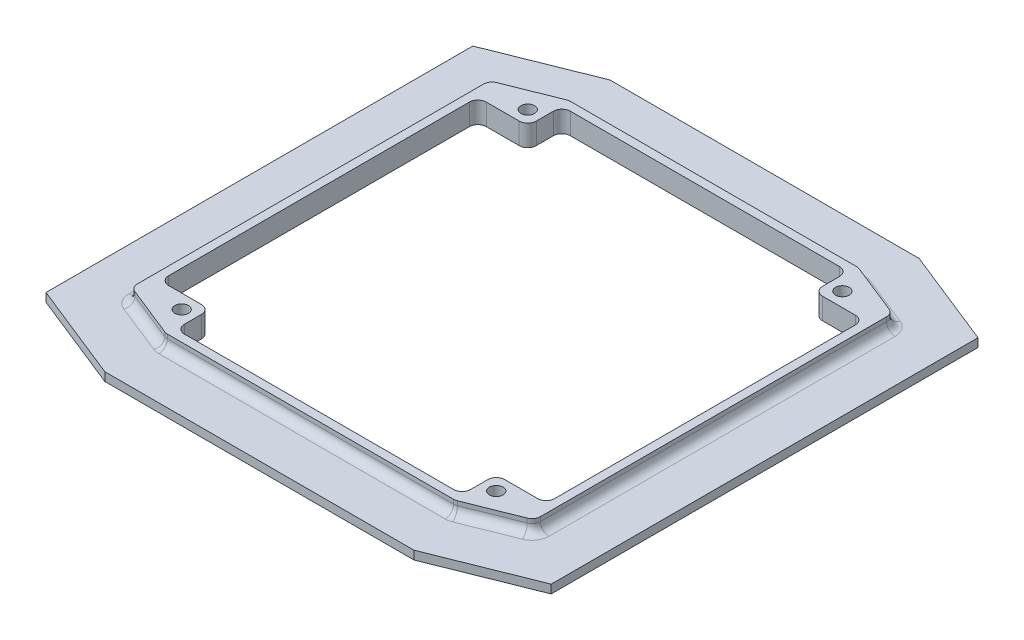
SolidWorks part; units mm, degrees
material "6061-T6 (SS)"
ref_plane "Front Plane" through (0, 0, 0) normal (0, 0, 1) x (1, 0, 0)
ref_plane "Top Plane" through (0, 0, 0) normal (0, 1, 0) x (1, 0, 0)
ref_plane "Right Plane" through (0, 0, 0) normal (1, 0, 0) x (0, 0, -1)
sketch "Sketch1" plane through (0, 0, 0) normal (0, 1, 0) x (1, 0, 0)
  line L5 (-35.5, 0) -> (0, 0) construction
  line L6 (-25.5, -35.5) -> (25.5, -35.5)
  line L10 (-35.5, -31.5) -> (-35.5, 31.5)
  line L11 (-25.5, 35.5) -> (25.5, 35.5)
  line L12 (35.5, -31.5) -> (35.5, 31.5)
  line L13 (0, 0) -> (0, 35.5) construction
  line L14 (25.5, -35.5) -> (35.5, -31.5)
  line L15 (25.5, 35.5) -> (35.5, 31.5)
  line L16 (-25.5, -35.5) -> (-35.5, -31.5)
  line L17 (-25.5, 35.5) -> (-35.5, 31.5)
  point P0 (0, 0)
  point P4 (35.5, -35.5)
  dimension "D3" = 4
  dimension "D2" = 10
  dimension "D4" = 71
extrude "Boss-Extrude1" add sketch "Sketch1" along normal mid plane 4.5
sketch "Sketch2" plane through (0, 2.25, 0) normal (0, 1, 0) x (1, 0, 0)
  line L16 (27.2332, -44.5) -> (44.5, -37.5933)
  line L17 (44.5, -37.5933) -> (44.5, 37.5933)
  line L18 (44.5, 37.5933) -> (27.2332, 44.5)
  line L19 (27.2332, 44.5) -> (-27.2332, 44.5)
  line L20 (-27.2332, 44.5) -> (-44.5, 37.5933)
  line L21 (-44.5, 37.5933) -> (-44.5, -37.5933)
  line L22 (-44.5, -37.5933) -> (-27.2332, -44.5)
  line L23 (-27.2332, -44.5) -> (27.2332, -44.5)
  line L24 (27.2332, -44.5) -> (44.5, -37.5933)
  line L25 (44.5, -37.5933) -> (44.5, 37.5933)
  line L26 (44.5, 37.5933) -> (27.2332, 44.5)
  line L27 (27.2332, 44.5) -> (-27.2332, 44.5)
  line L28 (-27.2332, 44.5) -> (-44.5, 37.5933)
  line L29 (-44.5, 37.5933) -> (-44.5, -37.5933)
  line L30 (-44.5, -37.5933) -> (-27.2332, -44.5)
  line L31 (-27.2332, -44.5) -> (27.2332, -44.5)
  dimension "D1" = 9
extrude "Boss-Extrude2" add sketch "Sketch2" along normal blind 1.5
mirror "Mirror1" about plane through (0, 0, 0) normal (0, 1, 0) of "Boss-Extrude2"
sketch "Sketch3" plane through (0, 0, 0) normal (0, 1, 0) x (1, 0, 0)
  line L16 (-25.2111, -34) -> (25.2111, -34)
  line L17 (25.2111, -34) -> (34, -30.4845)
  line L18 (34, -30.4845) -> (34, 30.4845)
  line L19 (34, 30.4845) -> (25.2111, 34)
  line L20 (25.2111, 34) -> (-25.2111, 34)
  line L21 (-25.2111, 34) -> (-34, 30.4845)
  line L22 (-34, 30.4845) -> (-34, -30.4845)
  line L23 (-34, -30.4845) -> (-25.2111, -34)
  line L24 (-25.2111, -34) -> (25.2111, -34)
  line L25 (25.2111, -34) -> (34, -30.4845)
  line L26 (34, -30.4845) -> (34, 30.4845)
  line L27 (34, 30.4845) -> (25.2111, 34)
  line L28 (25.2111, 34) -> (-25.2111, 34)
  line L29 (-25.2111, 34) -> (-34, 30.4845)
  line L30 (-34, 30.4845) -> (-34, -30.4845)
  line L31 (-34, -30.4845) -> (-25.2111, -34)
  dimension "D1" = 10.5
extrude "Cut-Extrude1" cut sketch "Sketch3" against normal through all both and the other way through all
sketch "Sketch5" plane through (0, 0, 0) normal (0, 0, 1) x (1, 0, 0)
  line L0 (0, 0) -> (0, 28.4264) construction
  line L1 (-27.2332, 3.75) -> (27.2332, 3.75) construction
  line L2 (-26, 3.75) -> (-18, 3.75)
  line L3 (-26, 3.75) -> (-26, 16.55)
  line L4 (-26, 16.55) -> (-18, 16.55)
  line L5 (-18, 3.75) -> (-18, 16.55)
  line L6 (-22, 16.55) -> (-22, 9.7096) construction
  line L7 (18, 3.75) -> (18, 16.55)
  line L8 (26, 16.55) -> (18, 16.55)
  line L9 (26, 3.75) -> (26, 16.55)
  line L10 (26, 3.75) -> (18, 3.75)
  dimension "D1" = 22
  dimension "D3" = 12.8
  dimension "D2" = 8
extrude "Boss-Extrude3" add sketch "Sketch5" against normal blind 1.5 from surface starting at face at (0, 3, 44.5)
extrude "Boss-Extrude4" add sketch "Sketch5<2>" along normal blind 1.5 from surface starting at face at (0, 3, -44.5)
sketch "Sketch5<2>" plane through (0, 0, 0) normal (0, 0, 1) x (1, 0, 0) same geometry as "Sketch5"
sketch "Sketch6" plane through (0, 0, 0) normal (0, 0, 1) x (1, 0, 0)
  line L0 (-22, 16.55) -> (-22, 13.85) construction
  line L1 (-18, 16.55) -> (-26, 16.55) construction
  line L2 (0, 0) -> (0, 25.5714) construction
  line L3 (-22, 13.85) -> (-22, 8.45) construction
  circle A0 centre (-22, 13.85) radius 1.2
  circle A1 centre (22, 13.85) radius 1.2
  circle A2 centre (-22, 8.45) radius 1.2
  circle A3 centre (22, 8.45) radius 1.2
  dimension "D1" = 2.4
  dimension "D2" = 2.7
  dimension "D3" = 5.4
extrude "Cut-Extrude3" cut sketch "Sketch6" against normal through all both and the other way through all
fillet "Fillet1" radius 1.5 35 edges at (35.5, 0, 31.5) (25.5, 0, 35.5) (0, 2.25, -35.5) (0, -2.25, -35.5) (35.5, 2.25, 0) (35.5, -2.25, 0) (-35.5, 2.25, 0) (-35.5, -2.25, 0) (0, 2.25, 35.5) (0, -2.25, 35.5) (-25.5, 0, -35.5) (-30.5, 2.25, -33.5) (-35.5, 0, -31.5) (-30.5, -2.25, -33.5) (35.5, 0, -31.5) (30.5, 2.25, -33.5) (25.5, 0, -35.5) (30.5, -2.25, -33.5) (30.5, 2.25, 33.5) (30.5, -2.25, 33.5) (-35.5, 0, 31.5) (-30.5, 2.25, 33.5) (-25.5, 0, 35.5) (-30.5, -2.25, 33.5) (-22, 3.75, -43) (22, 3.75, -43) (-22, 3.75, 43) (22, 3.75, 43) (26, 3.75, 43.75) (-18, 3.75, 43.75) (18, 3.75, 43.75) (-26, 3.75, 43.75) (18, 3.75, -43.75) (26, 3.75, -43.75) (-26, 3.75, -43.75)
sketch "Sketch7" plane through (0, 0, 0) normal (0, 1, 0) x (1, 0, 0)
  line L0 (16.5, 44.5) -> (-18, 44.5) construction
  line L1 (44.5, -44.5) -> (-44.5, -44.5)
  line L2 (44.5, -44.5) -> (44.5, 44.5)
  line L3 (44.5, 44.5) -> (-44.5, 44.5)
  line L4 (-44.5, -44.5) -> (-44.5, 44.5)
  line L5 (44.5, -44.5) -> (-44.5, 44.5) construction
  line L6 (44.5, 44.5) -> (-44.5, -44.5) construction
  line L7 (-44.5, 37.5933) -> (-44.5, -37.5933) construction
  point P0 (0, 0)
extrude "Cut-Extrude4" cut sketch "Sketch7" along normal through all
sketch "Sketch8" plane through (0, 0, 0) normal (0, 1, 0) x (1, 0, 0)
  line L0 (34, 30.4845) -> (25.2111, 34)
  line L1 (34, 30.4845) -> (34, 27.9845)
  line L2 (34, 30.4845) -> (34, -30.4845) construction
  line L3 (34, 27.9845) -> (25.2111, 27.9845)
  line L4 (25.2111, 27.9845) -> (25.2111, 34)
  line L5 (44.5, 0) -> (-44.5, 0) construction
  line L6 (-44.5, 37.5933) -> (-44.5, -37.5933) construction
  line L7 (0, -44.5) -> (0, 44.5) construction
  line L8 (27.2332, 44.5) -> (-27.2332, 44.5) construction
  line L9 (34, 30.4845) -> (25.2111, 30.4845) construction
  line L10 (-34, 30.4845) -> (-25.2111, 30.4845) construction
  line L11 (-25.2111, 27.9845) -> (-25.2111, 34)
  line L12 (-34, 27.9845) -> (-25.2111, 27.9845)
  line L13 (-34, 30.4845) -> (-34, 27.9845)
  line L14 (-34, 30.4845) -> (-25.2111, 34)
  line L15 (34, -30.4845) -> (25.2111, -30.4845) construction
  line L16 (25.2111, -27.9845) -> (25.2111, -34)
  line L17 (34, -27.9845) -> (25.2111, -27.9845)
  line L18 (34, -30.4845) -> (34, -27.9845)
  line L19 (34, -30.4845) -> (25.2111, -34)
  line L20 (-34, -30.4845) -> (-25.2111, -30.4845) construction
  line L21 (-34, -30.4845) -> (-25.2111, -34)
  line L22 (-34, -30.4845) -> (-34, -27.9845)
  line L23 (-34, -27.9845) -> (-25.2111, -27.9845)
  line L24 (-25.2111, -27.9845) -> (-25.2111, -34)
  circle A0 centre (27.7111, 30.4845) radius 1.2
  circle A1 centre (-27.7111, 30.4845) radius 1.2
  circle A2 centre (27.7111, -30.4845) radius 1.2
  circle A3 centre (-27.7111, -30.4845) radius 1.2
  point P14 (0, 0)
  point P20 (0, 0)
  dimension "D2" = 2.4
  dimension "D1" = 2.5
  dimension "D3" = 2.5
extrude "Boss-Extrude5" add sketch "Sketch8" against normal up to surface (3.75 mm away) up to face at (0, -3.75, 0)
fillet "Fillet2" radius 1.5 12 edges at (25.2111, -1.875, -34) (25.2111, -1.875, -27.9845) (34, -1.875, -27.9845) (-34, -1.875, -27.9845) (-25.2111, -1.875, -27.9845) (-25.2111, -1.875, -34) (-34, -1.875, 27.9845) (-25.2111, -1.875, 27.9845) (-25.2111, -1.875, 34) (34, -1.875, 27.9845) (25.2111, -1.875, 27.9845) (25.2111, -1.875, 34)
